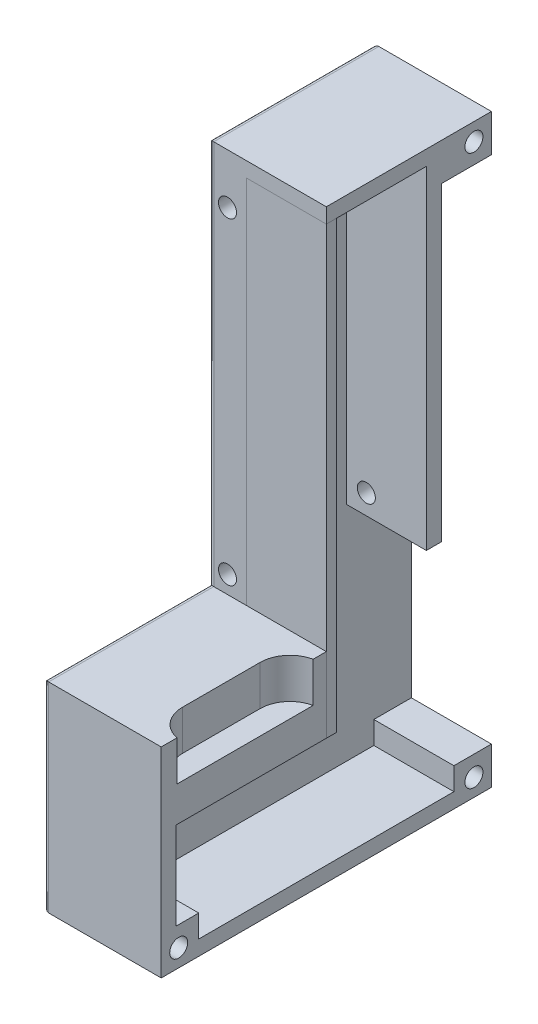
SolidWorks part; units mm, degrees
material "ABS"
ref_plane "Front" through (0, 0, 0) normal (0, 0, 1) x (1, 0, 0)
ref_plane "Top" through (0, 0, 0) normal (0, 1, 0) x (1, 0, 0)
ref_plane "Right" through (0, 0, 0) normal (1, 0, 0) x (0, 0, -1)
sketch "ｽｹｯﾁ1" plane through (0, 0, 0) normal (1, 0, 0) x (0, 0, -1)
  line L0 (23, 92) -> (0, 92)
  line L1 (33, 92) -> (23, 92)
  line L2 (33, 92) -> (33, -25)
  line L3 (33, -25) -> (23, -25)
  line L4 (23, 92) -> (23, -25)
  line L5 (0, 92) -> (0, -25)
  line L6 (0, -25) -> (23, -25)
  line L7 (0, -25) -> (-33, -25)
  line L8 (-33, -25) -> (-33, 0)
  line L9 (-33, 0) -> (0, 0)
  dimension "D1" = 117
  dimension "D2" = 10
  dimension "D3" = 33
  dimension "D4" = 23
  dimension "D5" = 25
extrude "ﾎﾞｽ - 押し出し1" add sketch "ｽｹｯﾁ1" along normal blind 77 contours L9 L8 L7 L5 | L5 L6 L4 L0 | L1 L4 L3 L2 region at (0, 33.5, -11.5) region at (0, 33.5, -28) region at (0, -12.5, 16.5)
sketch "ｽｹｯﾁ2" plane through (0, 0, -33) normal (0, 0, -1) x (-1, 0, 0)
  line L1 (-7.5, 22.5) -> (-69.5, 22.5)
  line L2 (-7.5, 22.5) -> (-7.5, 84.5)
  line L3 (-7.5, 84.5) -> (-69.5, 84.5)
  line L4 (-69.5, 22.5) -> (-69.5, 84.5)
  line L5 (-7.5, 22.5) -> (-69.5, 84.5) construction
  line L6 (-7.5, 84.5) -> (-69.5, 22.5) construction
  line L8 (0, 92) -> (0, -25) construction
  line L9 (-77, 92) -> (0, 92) construction
  point P0 (-38.5, 53.5)
  dimension "D1" = 62
  dimension "D2" = 62
  dimension "D3" = 7.5
  dimension "D4" = 7.5
extrude "ｶｯﾄ - 押し出し1" cut sketch "ｽｹｯﾁ2" against normal blind 10
sketch "ｽｹｯﾁ3" plane through (0, 92, 0) normal (0, 1, 0) x (1, 0, 0)
  line L1 (0, 33) -> (0, 0) construction
  line L2 (77, 0) -> (0, 0) construction
  circle A0 centre (37.5, 12.5) radius 8.1
  dimension "D1" = 16.2
  dimension "D2" = 37.5
  dimension "D3" = 12.5
extrude "ｶｯﾄ - 押し出し2" cut sketch "ｽｹｯﾁ3" against normal blind 10
sketch "ｽｹｯﾁ4" plane through (0, 0, -33) normal (0, 0, -1) x (-1, 0, 0)
  line L0 (-77, -25) -> (0, -25) construction
  line L1 (-7.5, 22.5) -> (-69.5, 22.5)
  line L2 (-7.5, 22.5) -> (-7.5, -17.5)
  line L3 (-7.5, -17.5) -> (-69.5, -17.5)
  line L4 (-69.5, 22.5) -> (-69.5, -17.5)
  dimension "D1" = 7.5
extrude "ｶｯﾄ - 押し出し3" cut sketch "ｽｹｯﾁ4" against normal offset from surface (58.5 mm away) 7.5 up to face at (38.5, -12.5, 33)
sketch "ｽｹｯﾁ5" plane through (0, 0, 0) normal (0, 1, 0) x (1, 0, 0)
  line L1 (50.25, -2.5) -> (24.75, -2.5)
  line L2 (56.25, -8.5) -> (56.25, -24)
  line L3 (50.25, -30) -> (24.75, -30)
  line L4 (18.75, -8.5) -> (18.75, -24)
  line L5 (56.25, -2.5) -> (18.75, -30) construction
  line L6 (56.25, -30) -> (18.75, -2.5) construction
  line L7 (0, -33) -> (0, 0) construction
  line L11 (77, -33) -> (0, -33)
  line L12 (77, -33) -> (77, 0)
  line L13 (77, 0) -> (0, 0)
  line L14 (0, -33) -> (0, 0)
  arc A0 (18.75, -8.5) -> (24.75, -2.5) centre (24.75, -8.5) cw
  arc A1 (56.25, -8.5) -> (50.25, -2.5) centre (50.25, -8.5) ccw
  arc A2 (56.25, -24) -> (50.25, -30) centre (50.25, -24) cw
  arc A3 (24.75, -30) -> (18.75, -24) centre (24.75, -24) cw
  point P0 (37.5, -16.25)
  dimension "D5" = 6
  dimension "D1" = 27.5
  dimension "D2" = 37.5
  dimension "D3" = 37.5
  dimension "D4" = 3
extrude "ﾎﾞｽ - 押し出し2" add sketch "ｽｹｯﾁ5" along normal blind 15
sketch "ｽｹｯﾁ6" plane through (0, 0, 0) normal (0, 1, 0) x (1, 0, 0)
  line L20 (43.25, -30) -> (43.25, -2.5)
  line L21 (51.25, -30) -> (51.25, -2.5839)
  line L22 (43.25, -25.25) -> (51.25, -25.25)
  line L24 (50.25, -2.5) -> (24.75, -2.5)
  line L25 (56.25, -24) -> (56.25, -8.5)
  line L26 (24.75, -30) -> (50.25, -30)
  line L27 (18.75, -8.5) -> (18.75, -24)
  line L28 (50.25, -2.5) -> (24.75, -2.5)
  line L29 (56.25, -24) -> (56.25, -8.5)
  line L30 (24.75, -30) -> (50.25, -30)
  line L31 (18.75, -8.5) -> (18.75, -24)
  line L32 (43.25, -7.25) -> (51.25, -7.25)
  arc A21 (24.75, -2.5) -> (18.75, -8.5) centre (24.75, -8.5) ccw
  arc A22 (56.25, -8.5) -> (50.25, -2.5) centre (50.25, -8.5) ccw
  arc A23 (50.25, -30) -> (56.25, -24) centre (50.25, -24) ccw
  arc A24 (18.75, -24) -> (24.75, -30) centre (24.75, -24) ccw
  arc A25 (24.75, -2.5) -> (18.75, -8.5) centre (24.75, -8.5) ccw
  arc A26 (56.25, -8.5) -> (50.25, -2.5) centre (50.25, -8.5) ccw
  arc A27 (50.25, -30) -> (56.25, -24) centre (50.25, -24) ccw
  arc A28 (18.75, -24) -> (24.75, -30) centre (24.75, -24) ccw
  arc M14 (18.9405, -25.5) -> (24.75, -30) centre (24.75, -24) ccw
  line M15 (24.75, -30) -> (50.25, -30)
  arc M16 (50.25, -30) -> (56.0595, -25.5) centre (50.25, -24) ccw
  line M17 (56.0595, -25.5) -> (18.9405, -25.5)
  dimension "D2" = 13
  dimension "D3" = 8
  dimension "D4" = 18
  dimension "D5" = 4.75
  dimension "D1" = 0
extrude "ﾎﾞｽ - 押し出し3" add sketch "ｽｹｯﾁ6" along normal blind 7 contours L31 A28 L20 L28 A25 M17 | L20 M15 M17 M14 | L21 L20 M16 M17 M15 | A27 L29 A26 L21 M17 | L21 M16 M17 | L21 A26 L28 L20 L32 region at (31.1538, 0, 14.1394) region at (47.2472, 0, 4.8767) region at (47.2471, 0, 27.7483) region at (31.8101, 0, 27.6791) region at (53.6635, 0, 14.7193) region at (53.1589, 0, 27.2657)
sketch "ｽｹｯﾁ7" plane through (0, 0, 0) normal (0, 0, 1) x (1, 0, 0)
  line L0 (0, 92) -> (0, 15) construction
  line L1 (69.5, 89) -> (7.5, 89)
  line L2 (69.5, 89) -> (69.5, 22.5)
  line L3 (69.5, 22.5) -> (7.5, 22.5)
  line L4 (7.5, 89) -> (7.5, 22.5)
  line L5 (69.5, 89) -> (7.5, 22.5) construction
  line L6 (69.5, 22.5) -> (7.5, 89) construction
  line L7 (77, 92) -> (0, 92) construction
  line L9 (69.5, 22.5) -> (7.5, 22.5) construction
  line L10 (69.5, 84.5) -> (69.5, -17.5) construction
  point P0 (38.5, 55.75)
  dimension "D1" = 7.5
  dimension "D2" = 3
extrude "ｶｯﾄ - 押し出し4" cut sketch "ｽｹｯﾁ7" against normal offset from surface (20 mm away) 3 up to face at (38.5, 53.5, -23)
sketch "ｽｹｯﾁ8" plane through (0, 89, 0) normal (0, -1, 0) x (-1, 0, 0)
  line L0 (-69.5, 20) -> (-69.5, 0) construction
  line L1 (-7.5, 0) -> (-69.5, 0)
  line L2 (-7.5, 0) -> (-7.5, 2)
  line L3 (-7.5, 2) -> (-69.5, 2)
  line L4 (-69.5, 0) -> (-69.5, 2)
  dimension "D1" = 2
extrude "ﾎﾞｽ - 押し出し4" add sketch "ｽｹｯﾁ8" along normal up to vertex (89 mm away) separate body up to point (43.25, 0, 7.25)
sketch "ｽｹｯﾁ9" plane through (0, 0, 0) normal (-1, 0, 0) x (0, 0, 1)
  line L0 (-33, 92) -> (0, 92) construction
  line L1 (-33, 92) -> (-33, -25) construction
  line L2 (-33, -25) -> (33, -25) construction
  line L3 (33, -25) -> (33, 15) construction
  circle A0 centre (-29.5, 88.5) radius 1.8
  circle A1 centre (-29.5, -21.5) radius 1.8
  circle A2 centre (29.5, -21.5) radius 1.8
  dimension "D3" = 3.6
  dimension "D5" = 3.5
  dimension "D1" = 3.5
  dimension "D2" = 3.5
  dimension "D4" = 3.5
extrude "ｶｯﾄ - 押し出し5" cut sketch "ｽｹｯﾁ9" against normal through all
sketch "ｽｹｯﾁ10" plane through (0, 0, 0) normal (0, 0, 1) x (1, 0, 0)
  line L0 (77, 92) -> (0, 92) construction
  line L1 (7.5, 15) -> (0, 15) construction
  line L2 (0, 92) -> (0, 15) construction
  line L3 (77, 92) -> (77, 15) construction
  circle A0 centre (3.75, 82) radius 1.8
  circle A1 centre (73.25, 82) radius 1.8
  circle A2 centre (73.25, 18.5) radius 1.8
  circle A3 centre (3.75, 18.5) radius 1.8
  dimension "D3" = 3.6
  dimension "D1" = 3.5
  dimension "D2" = 10
  dimension "D4" = 3.75
  dimension "D5" = 3.75
extrude "ｶｯﾄ - 押し出し6" cut sketch "ｽｹｯﾁ10" against normal through all
sketch "ｽｹｯﾁ12" plane through (0, 0, -23) normal (0, 0, -1) x (-1, 0, 0)
  line L0 (-69.5, 84.5) -> (-69.5, 22.5) construction
  line L1 (-7.5, 84.5) -> (-69.5, 84.5) construction
  circle A0 centre (-66.5, 81.5) radius 1.8
  circle A1 centre (-11.5, 81.5) radius 1.8
  circle A2 centre (-11.5, 26.5) radius 1.8
  circle A3 centre (-66.5, 26.5) radius 1.8
  dimension "D3" = 3.6
  dimension "D1" = 55
  dimension "D2" = 55
  dimension "D4" = 3
  dimension "D5" = 3
extrude "ｶｯﾄ - 押し出し7" cut sketch "ｽｹｯﾁ12" against normal up to next (3 mm away)
sketch "ｽｹｯﾁ13" plane through (0, 0, -33) normal (0, 0, -1) x (-1, 0, 0)
  line L0 (0, 92) -> (0, -25) construction
  line L1 (0, 30.5) -> (-7.5, 30.5)
  line L2 (0, 30.5) -> (0, 42)
  line L3 (0, 42) -> (-7.5, 42)
  line L4 (-7.5, 30.5) -> (-7.5, 42)
  line L5 (-7.5, -17.5) -> (-7.5, 84.5) construction
  line L6 (-69.5, 22.5) -> (-7.5, 22.5) construction
  point P10 (-3.75, 42)
  dimension "D1" = 8
  dimension "D2" = 19.5
extrude "ｶｯﾄ - 押し出し8" cut sketch "ｽｹｯﾁ13" against normal blind 10
sketch "ｽｹｯﾁ14" plane through (0, 0, -23) normal (0, 0, -1) x (-1, 0, 0)
  line L0 (-69.5, 78) -> (-63, 78)
  line L1 (-69.5, 84.5) -> (-69.5, 22.5) construction
  line L2 (-63, 78) -> (-63, 84.5)
  line L3 (-7.5, 84.5) -> (-69.5, 84.5) construction
  line L4 (-15.5, 84.5) -> (-15.5, 78)
  line L5 (-15.5, 78) -> (-7.5, 78)
  line L6 (-7.5, 42) -> (-7.5, 84.5) construction
  line L8 (-69.5, 22.5) -> (-7.5, 22.5) construction
  line L10 (-7.5, 30.5) -> (-15.5, 30.5)
  line L11 (-15.5, 30.5) -> (-15.5, 22.5)
  line L12 (-15.5, 22.5) -> (-7.5, 22.5)
  line L13 (-7.5, 22.5) -> (-7.5, 30.5)
  line L14 (-69.5, 30.5) -> (-69.5, 22.5)
  line L16 (-63, 84.5) -> (-69.5, 84.5)
  line L17 (-69.5, 84.5) -> (-69.5, 78)
  line L18 (-15.5, 84.5) -> (-7.5, 84.5)
  line L19 (-7.5, 84.5) -> (-7.5, 78)
  line L20 (-69.5, 30.5) -> (-63, 30.5)
  line L21 (-63, 30.5) -> (-63, 22.5)
  line L22 (-63, 22.5) -> (-69.5, 22.5)
  circle A7 centre (-11.5, 81.5) radius 1.8
  circle A8 centre (-11.5, 81.5) radius 1.8
  circle A10 centre (-11.5, 26.5) radius 1.8
  circle A11 centre (-11.5, 26.5) radius 1.8
  circle A13 centre (-66.5, 81.5) radius 1.8
  circle A14 centre (-66.5, 81.5) radius 1.8
  circle A16 centre (-66.5, 26.5) radius 1.8
  circle A17 centre (-66.5, 26.5) radius 1.8
  dimension "D1" = 6.5
  dimension "D2" = 6.5
  dimension "D3" = 0
  dimension "D4" = 0
  dimension "D5" = 0
  dimension "D6" = 0
extrude "ﾎﾞｽ - 押し出し6" add sketch "ｽｹｯﾁ14" along normal blind 2
sketch "ｽｹｯﾁ15" plane through (77, 0, 0) normal (1, 0, 0) x (0, 0, -1)
  line L12 (0, 15) -> (-33, 15)
  line L13 (-33, 15) -> (-33, -25)
  line L14 (-33, -25) -> (33, -25)
  line L15 (33, -25) -> (33, 92)
  line L16 (33, 92) -> (0, 92)
  line L17 (0, 92) -> (0, 15)
  line L18 (0, 15) -> (-33, 15)
  line L19 (-33, 15) -> (-33, -25)
  line L20 (-33, -25) -> (33, -25)
  line L21 (33, -25) -> (33, 92)
  line L22 (33, 92) -> (0, 92)
  line L23 (0, 92) -> (0, 15)
  dimension "D1" = 0
extrude "ｶｯﾄ - 押し出し9" cut sketch "ｽｹｯﾁ15" against normal blind 53.5
sketch "ｽｹｯﾁ17" plane through (0, -17.5, 0) normal (0, 1, 0) x (1, 0, 0)
  line L0 (23.5, -25.5) -> (23.5, 33) construction
  line L1 (7.5, -25.5) -> (23.5, -25.5)
  line L2 (7.5, -25.5) -> (7.5, 25.5)
  line L3 (7.5, 25.5) -> (23.5, 25.5)
  line L4 (23.5, -25.5) -> (23.5, 25.5)
  line L5 (23.5, 33) -> (7.5, 33) construction
  dimension "D1" = 7.5
extrude "ｶｯﾄ - 押し出し11" cut sketch "ｽｹｯﾁ17" against normal offset from surface (4.5 mm away) 3 up to face at (11.75, -25, 0)
sketch "ｽｹｯﾁ18" plane through (0, 0, 25.5) normal (0, 0, -1) x (-1, 0, 0)
  line L0 (-23.5, 0) -> (-23.5, -22) construction
  line L1 (-7.5, 0) -> (-23.5, 0)
  line L2 (-7.5, 0) -> (-7.5, -17.5)
  line L3 (-7.5, -17.5) -> (-23.5, -17.5)
  line L4 (-23.5, 0) -> (-23.5, -17.5)
  line L6 (-23.5, -25) -> (0, -25) construction
  dimension "D1" = 7.5
extrude "ｶｯﾄ - 押し出し12" cut sketch "ｽｹｯﾁ18" against normal offset from surface (4.5 mm away) 3 up to face at (11.75, -5, 33)
fillet "ﾌｨﾚｯﾄ1" radius 1 10 edges at (0, -5, 33) (0, 15, 16.5) (0, -25, 0) (0, 2.75, -33) (0, 92, -16.5) (0, 67, -33) (0, 42, -28) (0, 30.5, -28) (0, 36.25, -23) (0, 53.5, 0)
